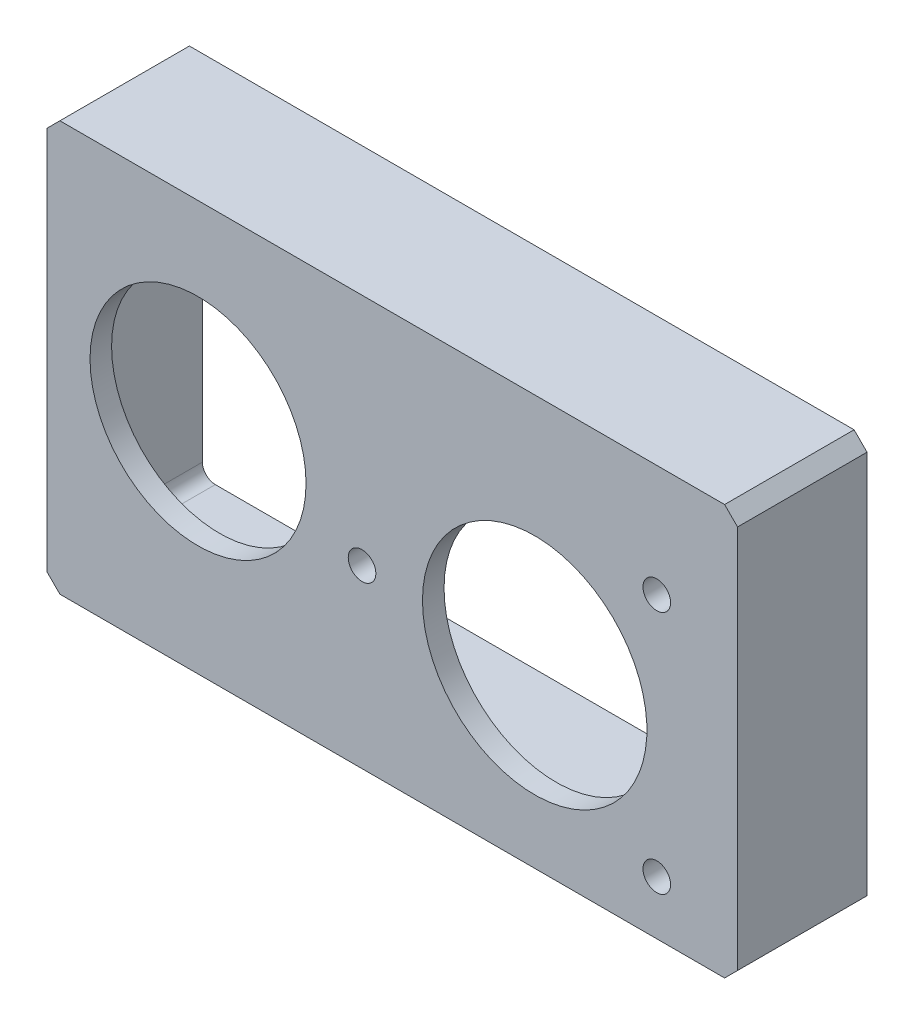
SolidWorks part; units mm, degrees
ref_plane "前视基准面" through (0, 0, 0) normal (0, 0, 1) x (1, 0, 0)
ref_plane "上视基准面" through (0, 0, 0) normal (0, 1, 0) x (1, 0, 0)
ref_plane "右视基准面" through (0, 0, 0) normal (1, 0, 0) x (0, 0, -1)
other "Configuration Table"
sketch "草图1" plane through (0, 0, 0) normal (0, 0, 1) x (1, 0, 0)
  line L2 (0, 0) -> (0, -60)
  line L5 (160, -60) -> (160, 35)
  line L6 (160, 35) -> (68, 35)
  line L8 (68, 35) -> (0, 35)
  line L9 (0, 35) -> (0, 0)
  line L10 (160, -60) -> (0, -60)
  dimension "D1" = 160
  dimension "D4" = 95
extrude "凸台-拉伸1" add sketch "草图1" along normal blind 30
sketch "草图4" plane through (0, 0, 0) normal (0, 0, -1) x (-1, 0, 0)
  line L0 (0, 35) -> (0, -60) construction
  line L1 (-6, -50) -> (-148, -50)
  line L2 (-6, -50) -> (-6, 25)
  line L3 (-6, 25) -> (-148, 25)
  line L4 (-148, -50) -> (-148, 25)
  line L5 (-160, 35) -> (0, 35) construction
  circle A0 centre (-113, -19.25) radius 27.5 construction
  dimension "D1" = 55
  dimension "D2" = 75
  dimension "D3" = 142
  dimension "D4" = 6
  dimension "D5" = 10
extrude "切除-拉伸2" cut sketch "草图4" against normal blind 25
sketch "草图5" plane through (0, 0, 25) normal (0, 0, -1) x (-1, 0, 0)
  circle A0 centre (-113, -19.25) radius 26
  dimension "D1" = 52
extrude "切除-拉伸3" cut sketch "草图5" against normal through all
chamfer "倒角3" distance 3 angle 45 4 edges at (160, -60, 15) (160, 35, 15) (0, -60, 15) (0, 35, 15)
fillet "圆角2" radius 3 4 edges at (148, 25, 12.5) (148, -50, 12.5) (6, 25, 12.5) (6, -50, 12.5)
sketch "草图7" plane through (0, 0, 25) normal (0, 0, -1) x (-1, 0, 0)
  circle A2 centre (-73, -19.25) radius 3.2
  circle A3 centre (-73, -19.25) radius 3.2
  circle A5 centre (-141.2843, -47.5343) radius 3.2
  circle A6 centre (-141.2843, -47.5343) radius 3.2
  circle A8 centre (-141.2843, 9.0343) radius 3.2
  circle A9 centre (-141.2843, 9.0343) radius 3.2
  dimension "D1" = 0.6
  dimension "D2" = 0.6
  dimension "D3" = 0.6
extrude "切除-拉伸4" cut sketch "草图7" against normal through all
sketch "草图8" plane through (0, 0, 25) normal (0, 0, -1) x (-1, 0, 0)
  circle A0 centre (-35, -9.275) radius 25.025
  dimension "D1" = 50.05
extrude "切除-拉伸5" cut sketch "草图8" against normal through all
sketch "草图9" plane through (0, 0, 0) normal (0, 0, -1) x (-1, 0, 0)
  circle A0 centre (-141.2843, -47.5343) radius 5.25
  dimension "D1" = 10.5
extrude "切除-拉伸6" cut sketch "草图9" against normal up to surface (25 mm away) up to face at (9.975, -9.275, 25)
hole_wizard "M6 螺纹孔1" positions "草图10" profile "草图11" tap size "M6" standard "GB"
sketch "草图10" plane through (0, 0, 0) normal (0, 0, -1) x (-1, 0, 0)
  point P0 (-154, 29)
  point P3 (-80, 29)
  point P6 (-6, 29)
  point P12 (-154, -54)
  point P14 (-6, -54)
  point P19 (-65, -54)
sketch "草图11" plane through (154, 29, 0) normal (1, 0, 0) x (0, 1, 0)
  line L0 (0, 0) -> (0, 16.5022)
  line L1 (0, 16.5022) -> (2.5, 15)
  line L2 (2.5, 15) -> (2.5, 0)
  line L5 (2.5, 0) -> (0, 0)
  line L10 (0, 16.5022) -> (-2.5, 15) construction
  line L11 (0, -6.35) -> (0, 107.95) construction
  dimension "螺纹孔钻头直径" = 5
  dimension "螺纹孔钻头深度" = 15
  dimension "导头角度" = 118
cosmetic thread "孔螺蚊线1" parameters "D1"=12, "D2"=6
cosmetic thread "孔螺蚊线2" parameters "D1"=12, "D2"=6
cosmetic thread "孔螺蚊线3" parameters "D1"=12, "D2"=6
cosmetic thread "孔螺蚊线4" parameters "D1"=12, "D2"=6
cosmetic thread "孔螺蚊线5" parameters "D1"=12, "D2"=6
cosmetic thread "孔螺蚊线6" parameters "D1"=12, "D2"=6
